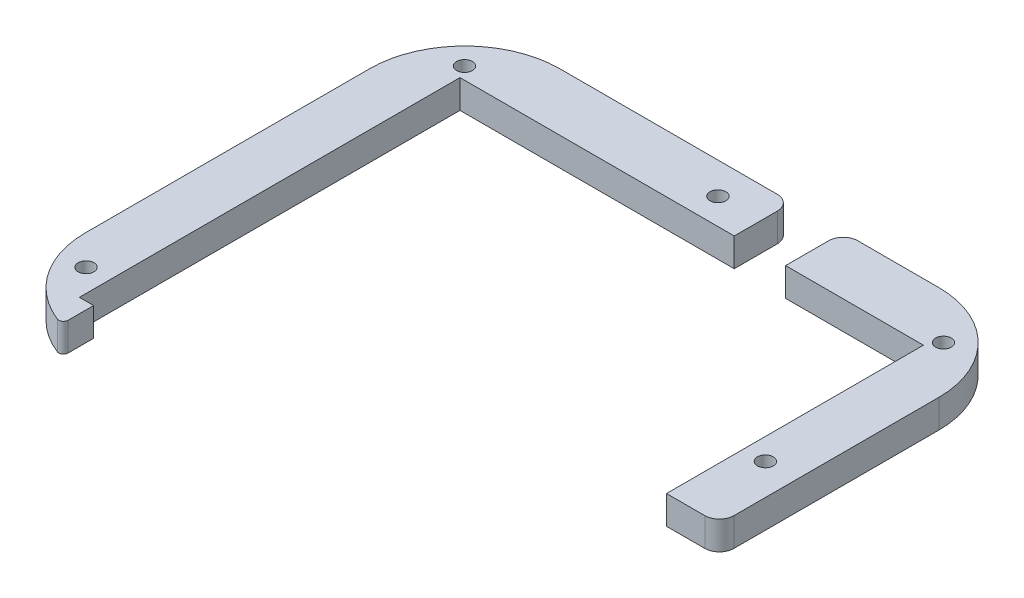
SolidWorks part; units mm, degrees
ref_plane "Front Plane" through (0, 0, 0) normal (0, 0, 1) x (1, 0, 0)
ref_plane "Top Plane" through (0, 0, 0) normal (0, 1, 0) x (1, 0, 0)
ref_plane "Right Plane" through (0, 0, 0) normal (1, 0, 0) x (0, 0, -1)
sketch "Sketch1" plane through (0, 0, 0) normal (0, 1, 0) x (1, 0, 0)
  line L0 (-60, 30) -> (-60, -30)
  line L1 (-40, 50) -> (40, 50)
  line L2 (-40, -50) -> (40, -50)
  line L3 (0, 50) -> (0, -50) construction
  line L4 (-60, 0) -> (94.7381, 0) construction
  line L5 (60, 0) -> (-94.7381, 0) construction
  line L6 (60, 30) -> (60, -30)
  arc A0 (-40, 50) -> (-60, 30) centre (-40, 30) ccw
  arc A1 (-40, -50) -> (-60, -30) centre (-40, -30) cw
  arc A2 (40, -50) -> (60, -30) centre (40, -30) ccw
  arc A3 (40, 50) -> (60, 30) centre (40, 30) cw
  dimension "D1" = 20
  dimension "D2" = 120
  dimension "D3" = 100
extrude "Boss-Extrude1" add sketch "Sketch1" along normal blind 6
sketch "Sketch2" plane through (0, 6, 0) normal (0, 1, 0) x (1, 0, 0)
  line L0 (0, 38) -> (0, -50) construction
  line L1 (-49, 38) -> (49, 38)
  line L2 (-49, 38) -> (-49, -50) construction
  line L3 (-46, -50) -> (49, -50)
  line L4 (49, 38) -> (49, -50)
  line L5 (-40, -50) -> (40, -50) construction
  line L6 (-49, -42.5) -> (-46, -42.5)
  line L7 (-46, -42.5) -> (-46, -50)
  line L8 (-49, 38) -> (-49, -42.5)
  dimension "D1" = 98
  dimension "D2" = 88
  dimension "D3" = 7.5
  dimension "D4" = 3
extrude "Cut-Extrude1" cut sketch "Sketch2" against normal through all
sketch "Sketch3" plane through (0, 6, 0) normal (0, 1, 0) x (1, 0, 0)
  line L0 (49, -47.8606) -> (49, 38) construction
  line L1 (49, -16.24) -> (74, -16.24)
  line L2 (49, -16.24) -> (49, -47.8606)
  line L3 (49, -47.8606) -> (74, -47.8606)
  line L4 (74, -16.24) -> (74, -47.8606)
  line L5 (40, 50) -> (-40, 50) construction
  dimension "D1" = 66.24
  dimension "D2" = 25
extrude "Cut-Extrude2" cut sketch "Sketch3" against normal through all
fillet "Fillet1" radius 3 1 edges at (60, 3, 16.24)
sketch "Sketch4" plane through (0, 6, 0) normal (0, 1, 0) x (1, 0, 0)
  line L0 (40, 50) -> (-40, 50) construction
  line L1 (19.9, 50) -> (8.9, 50)
  line L2 (19.9, 50) -> (19.9, 38)
  line L3 (19.9, 38) -> (8.9, 38)
  line L4 (8.9, 50) -> (8.9, 38)
  line L5 (49, 38) -> (-49, 38) construction
  line L6 (60, -13.24) -> (60, 30) construction
  dimension "D1" = 40.1
  dimension "D2" = 11
extrude "Cut-Extrude3" cut sketch "Sketch4" against normal through all
fillet "Fillet2" radius 3 1 edges at (8.9, 3, -50)
fillet "Fillet3" radius 3 1 edges at (19.9, 3, -50)
sketch "Sketch5" plane through (0, 6, 0) normal (0, 1, 0) x (1, 0, 0)
  line L0 (50.5586, 40.5086) -> (0, 0) construction
  line L1 (-50.5586, 40.5086) -> (0, 0) construction
  line L2 (0, 0) -> (-53.7093, -36.2274) construction
  line L3 (0, 0) -> (-47.8592, 0) construction
  circle A0 centre (53.475, 0) radius 1.75
  circle A1 centre (-53.7093, -36.2274) radius 1.75
  circle A2 centre (0, 43.45) radius 1.75
  circle A3 centre (50.5586, 40.5086) radius 1.75
  circle A4 centre (-50.5586, 40.5086) radius 1.75
  dimension "D1" = 3.5
  dimension "D2" = 43.45
  dimension "D3" = 64.7851
  dimension "D4" = 141.298
  dimension "D5" = 38.702
  dimension "D6" = 34
  dimension "D7" = 64.7851
  dimension "D8" = 64.7851
  dimension "D9" = 53.475
extrude "Cut-Extrude4" cut sketch "Sketch5" against normal through all
other "Move Face2" face at (50.5586, 0, -38.7586) face at (53.475, 0, 1.75) face at (19.9, 3, -42.5) face at (21.0893, 3, -48.8107) face at (31.45, 3, -50) face at (52.0711, 3, -42.0711) face at (60, 3, -8.38) face at (58.8107, 3, 15.0507) face at (49, 3, -10.88) face at (34.45, 3, -38) face at (53, 3, 16.24) offset 0.08 parameters "D1"=0.08
other "Move Face3" face at (-46, 3, 45.7894) face at (-47.5, 3, 42.5) face at (-49, 3, 2.25) face at (-49, 3, 2.25) face at (0, 0, -41.7) face at (-50.5586, 0, -42.2586) face at (-53.7093, 0, 37.9774) face at (-54.5623, 3, 40.6858) face at (-60, 3, 0) face at (-52.0711, 3, -42.0711) face at (-17.05, 3, -50) face at (7.7107, 3, -48.8107) face at (8.9, 3, -42.5) face at (-20.05, 3, -38) offset 0.08 parameters "D1"=0.08
fillet "Fillet4" radius 1 1 edges at (-45.92, 3, 49.1875)
